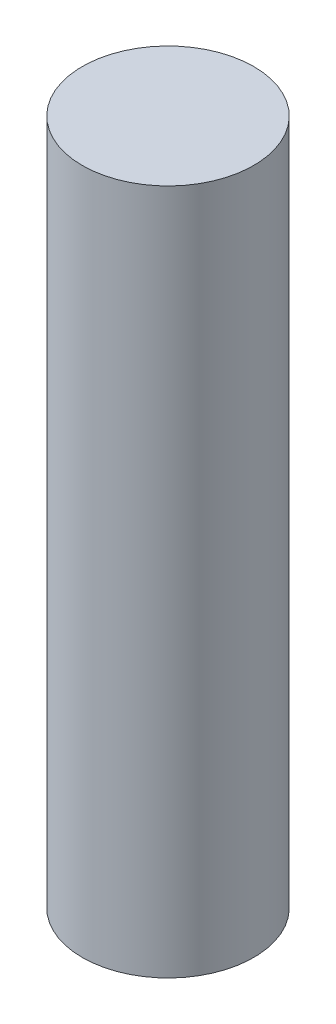
SolidWorks part; units mm, degrees
ref_plane "Front Plane" through (0, 0, 0) normal (0, 0, 1) x (1, 0, 0)
ref_plane "Top Plane" through (0, 0, 0) normal (0, 1, 0) x (1, 0, 0)
ref_plane "Right Plane" through (0, 0, 0) normal (1, 0, 0) x (0, 0, -1)
sketch "Sketch1" plane through (0, 0, 0) normal (0, 1, 0) x (1, 0, 0)
  circle A0 centre (0, 0) radius 12.7
  dimension "D1" = 25.4
extrude "Boss-Extrude1" add sketch "Sketch1" along normal blind 101.6
